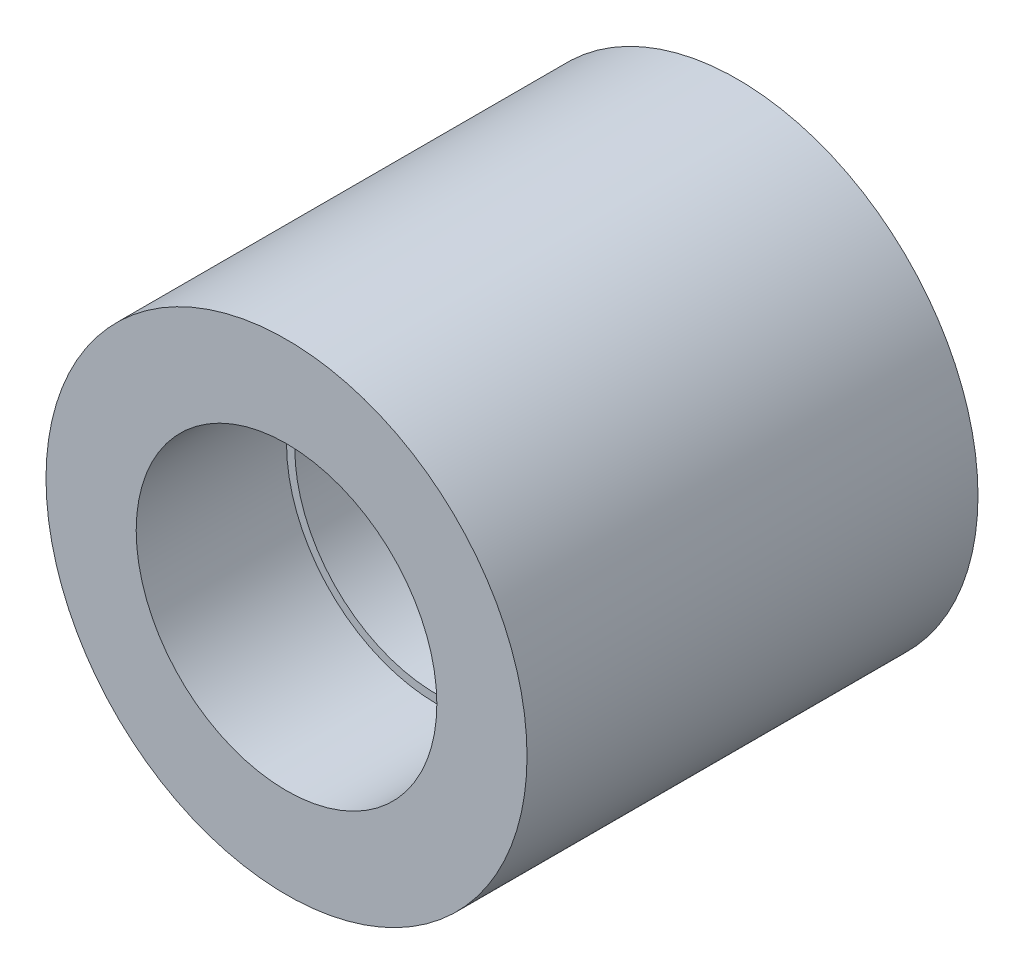
SolidWorks part; units mm, degrees
material "PLA"
ref_plane "Front Plane" through (0, 0, 0) normal (0, 0, 1) x (1, 0, 0)
ref_plane "Top Plane" through (0, 0, 0) normal (0, 1, 0) x (1, 0, 0)
ref_plane "Right Plane" through (0, 0, 0) normal (1, 0, 0) x (0, 0, -1)
sketch "Sketch1" plane through (0, 0, 0) normal (0, 0, 1) x (1, 0, 0)
  circle A0 centre (0, 0) radius 3.175
  circle A1 centre (0, 0) radius 5.08
  circle A2 centre (0, 0) radius 3
  dimension "D1" = 6.35
  dimension "D2" = 10.16
  dimension "D3" = 6
extrude "Boss-Extrude1" add sketch "Sketch1" along normal blind 3.175 contours A1 A0 region at (-4.9363, 0, 0)
extrude "Boss-Extrude2" add sketch "Sketch1<3>" against normal blind 6.35 contours A1 A0 | A0 A2 region at (-3.0852, 0, 0) region at (-4.9363, 0, 0)
sketch "Sketch1<3>" plane through (0, 0, 0) normal (0, 0, 1) x (1, 0, 0) same geometry as "Sketch1"
